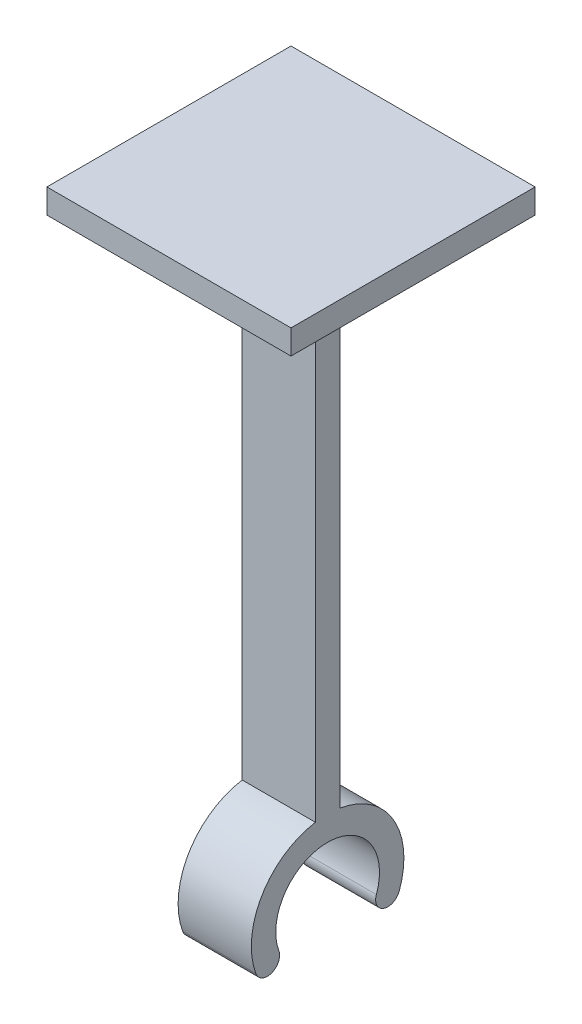
SolidWorks part; units mm, degrees
ref_plane "Front" through (0, 0, 0) normal (0, 0, 1) x (1, 0, 0)
ref_plane "Top" through (0, 0, 0) normal (0, 1, 0) x (1, 0, 0)
ref_plane "Right" through (0, 0, 0) normal (1, 0, 0) x (0, 0, -1)
sketch "Sketch1" plane through (0, 0, 0) normal (1, 0, 0) x (0, 0, -1)
  line L0 (0, 0) -> (-6.25, 0)
  line L1 (0, 0) -> (-5.8731, -2.1376)
  line L2 (0, 50) -> (0, -50) construction
  line L3 (0, 0) -> (5.8731, -2.1376)
  line L4 (-5.8731, -2.1376) -> (-4.9334, -1.7956)
  circle A0 centre (0, 0) radius 4.25
  circle A1 centre (0, 0) radius 6.25
  arc A2 (-5.8731, -2.1376) -> (-3.9937, -1.4536) centre (-4.9334, -1.7956) ccw
  arc A3 (5.8731, -2.1376) -> (3.9937, -1.4536) centre (4.9334, -1.7956) cw
  dimension "D1" = 20
  dimension "D3" = 12.5
  dimension "D4" = 8.5
  dimension "D2" = 1
extrude "Boss-Extrude1" add sketch "Sketch1" against normal blind 3 and the other way blind 3 contours L3 A1 L0 A0 | A3 L3 | L0 A1 L1 A0 | L1 A2 region at (0, -0.918, 5.2062) region at (0, 0.1505, 5.25) region at (0, -2.1944, 4.7882) region at (0, -2.1944, -4.7882)
sketch "Sketch2" plane through (0, 0, 0) normal (1, 0, 0) x (0, 0, -1)
  line L0 (0, 0) -> (0, 6.25)
  line L1 (0, 6.25) -> (0, 4.25)
  line L2 (0, 4.25) -> (-1, 4.25)
  line L4 (-1, 4.25) -> (1, 4.25)
  line L5 (-1, 4.25) -> (-1, 47.25)
  line L6 (-1, 47.25) -> (1, 47.25)
  line L7 (1, 4.25) -> (1, 47.25)
  arc A0 (5.8731, -2.1376) -> (-5.8731, -2.1376) centre (0, 0) ccw construction
  dimension "D1" = 2
  dimension "D2" = 1
  dimension "D3" = 2
  dimension "D4" = 43
extrude "Boss-Extrude2" add sketch "Sketch2" along normal blind 3 contours L4 L7 L6 L5 L2 region at (0, 25.75, 0)
sketch "Sketch3" plane through (0, 0, 0) normal (1, 0, 0) x (0, 0, -1)
  line L0 (0, 47.25) -> (-1, 47.25)
  line L1 (-1, 47.25) -> (1, 47.25) construction
  line L3 (-1, 47.25) -> (1, 47.25)
  line L4 (-1, 47.25) -> (-1, 4.25)
  line L5 (-1, 4.25) -> (1, 4.25)
  line L6 (1, 47.25) -> (1, 4.25)
  dimension "D1" = 1
  dimension "D2" = 43
  dimension "2" = 2
extrude "Boss-Extrude3" add sketch "Sketch3" against normal blind 3 contours L6 L3 L0 L4 L5 region at (0, 25.75, 0)
sketch "Sketch4" plane through (0, 47.25, 0) normal (0, 1, 0) x (1, 0, 0)
  line L1 (-10, -10) -> (10, -10)
  line L2 (-10, -10) -> (-10, 10)
  line L3 (-10, 10) -> (10, 10)
  line L4 (10, -10) -> (10, 10)
  line L5 (0, 10) -> (0, -10) construction
  line L6 (-10, 0) -> (10, 0) construction
  point P1 (0, 0)
  dimension "D1" = 20
  dimension "D2" = 20
extrude "Boss-Extrude4" add sketch "Sketch4" along normal blind 2
